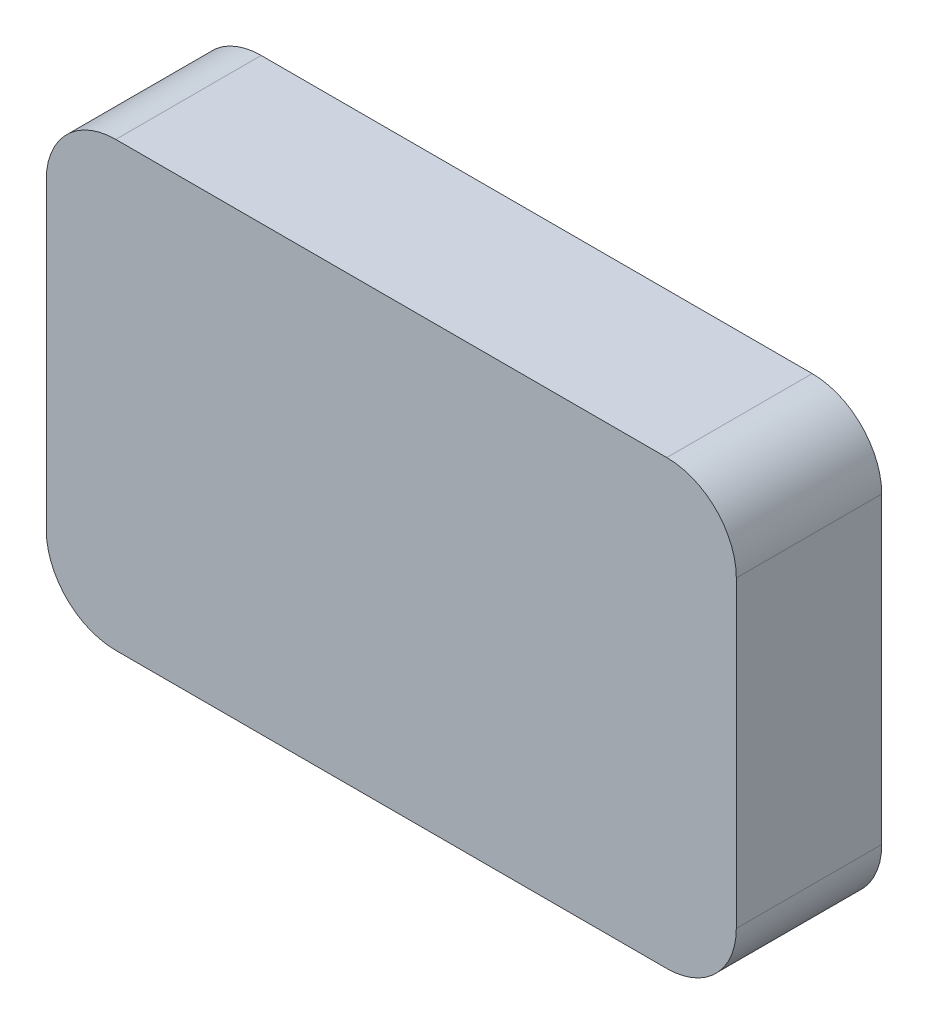
SolidWorks part; units mm, degrees
ref_plane "Plan de face" through (0, 0, 0) normal (0, 0, 1) x (1, 0, 0)
ref_plane "Plan de dessus" through (0, 0, 0) normal (0, 1, 0) x (1, 0, 0)
ref_plane "Plan de droite" through (0, 0, 0) normal (1, 0, 0) x (0, 0, -1)
sketch "Esquisse1" plane through (0, 0, 0) normal (0, 0, 1) x (1, 0, 0)
  line L1 (-39.6342, 31.8306) -> (39.6342, 31.8306)
  line L2 (-49.6342, 21.8306) -> (-49.6342, -21.8306)
  line L3 (-39.6342, -31.8306) -> (39.6342, -31.8306)
  line L4 (49.6342, 21.8306) -> (49.6342, -21.8306)
  line L5 (-49.6342, 31.8306) -> (49.6342, -31.8306) construction
  line L6 (-49.6342, -31.8306) -> (49.6342, 31.8306) construction
  arc A0 (-49.6342, -21.8306) -> (-39.6342, -31.8306) centre (-39.6342, -21.8306) ccw
  arc A1 (39.6342, -31.8306) -> (49.6342, -21.8306) centre (39.6342, -21.8306) ccw
  arc A2 (39.6342, 31.8306) -> (49.6342, 21.8306) centre (39.6342, 21.8306) cw
  arc A3 (-39.6342, 31.8306) -> (-49.6342, 21.8306) centre (-39.6342, 21.8306) ccw
  point P0 (0, 0)
  dimension "D1" = 10
sketch "profil" plane through (0, 0, 0) normal (1, 0, 0) x (0, 0, -1)
  line L0 (0, -30.2306) -> (9.1225, -30.2306)
  line L1 (9.1225, -30.2306) -> (17.9182, -25.6306)
  line L3 (17.9182, -31.8306) -> (0, -31.8306)
  line L4 (0, -31.8306) -> (0, -30.2306)
  line L6 (0, -21.8306) -> (0, -31.8306) construction
  line L7 (0, -31.8306) -> (0, 31.8306) construction
  line L8 (17.9182, -25.6306) -> (17.9182, -27.2306)
  line L9 (17.9182, -30.2306) -> (17.9182, -31.8306)
  arc A0 (17.9182, -27.2306) -> (17.9182, -30.2306) centre (17.9182, -28.7306) ccw
  point P7 (0, -31.8306)
  point P10 (0, 0)
  point P11 (0, -31.8306)
  dimension "D1" = 3
  dimension "D2" = 1.6
sweep "Balayage1" add profiles "profil" path "Esquisse1"
extrude "Boss.-Extru.1" add sketch "Esquisse1<3>" along normal blind 3
sketch "Esquisse1<3>" plane through (0, 0, 0) normal (0, 0, 1) x (1, 0, 0) same geometry as "Esquisse1"
fillet "Congé1" radius 2 9 edges at (-45.5739, 27.7703, 0) (-48.0342, 0, 0) (-45.5739, -27.7703, 0) (-19.8171, -30.2306, 0) (19.8171, -30.2306, 0) (45.5739, -27.7703, 0) (48.0342, 0, 0) (45.5739, 27.7703, 0) (0, 30.2306, 0)
equation "\"buse\"=0.4"
equation "\"coque\"= \"buse\" * 4"
equation "\"diam_silicone\"=3"
equation "\"D1@profil\" = \"diam_silicone\""
